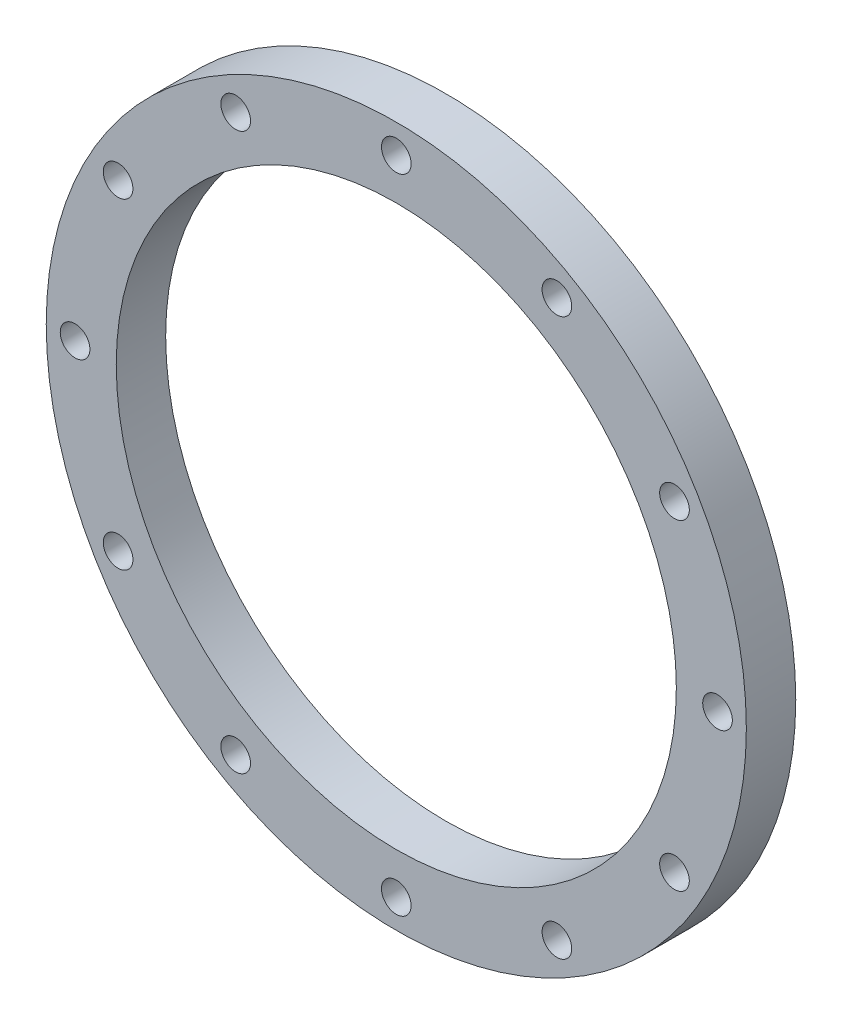
SolidWorks part; units mm, degrees
ref_plane "前视基准面" through (0, 0, 0) normal (0, 0, 1) x (1, 0, 0)
ref_plane "上视基准面" through (0, 0, 0) normal (0, 1, 0) x (1, 0, 0)
ref_plane "右视基准面" through (0, 0, 0) normal (1, 0, 0) x (0, 0, -1)
sketch "草图1" plane through (0, 0, 0) normal (0, 0, 1) x (1, 0, 0)
  circle A0 centre (0, 0) radius 42.5
  circle A1 centre (0, 0) radius 34
  dimension "D1" = 85
  dimension "D2" = 68
extrude "凸台-拉伸1" add sketch "草图1" along normal blind 6
hole_wizard "打孔尺寸(%根据)内六角圆柱头螺钉的类型1" positions "草图3" profile "草图2" counterbore size "M3" standard "GB" end condition through all
sketch "草图3" plane through (0, 0, 0) normal (0, 0, -1) x (-1, 0, 0)
  line L0 (0, 0) -> (0, 45.7551) construction
  circle A0 centre (0, 0) radius 39 construction
  point P0 (0, 39)
  dimension "D1" = 78
sketch "草图2" plane through (0, 39, 0) normal (1, 0, 0) x (0, 1, 0)
  line L0 (0, 0) -> (0, 6)
  line L1 (0, 6) -> (1.8, 6)
  line L3 (1.8, 6) -> (1.8, 3.4)
  line L4 (1.8, 3.4) -> (3, 3.4)
  line L5 (3, 3.4) -> (3, 0)
  line L7 (3, 0) -> (0, 0)
  line L11 (0, -6.35) -> (0, 107.95) construction
  dimension "通孔孔直径" = 3.6
  dimension "通孔孔深度" = 6
  dimension "柱形沉头孔直径" = 6
  dimension "柱形沉头孔深度" = 3.4
ref_axis "基准轴1" through (0, 0, 6) along (0, 0, -1)
pattern_circular "阵列(圆周)1" count 12 over 360 about axis through (0, 0, 6) along (0, 0, -1) of "打孔尺寸(%根据)内六角圆柱头螺钉的类型1"
